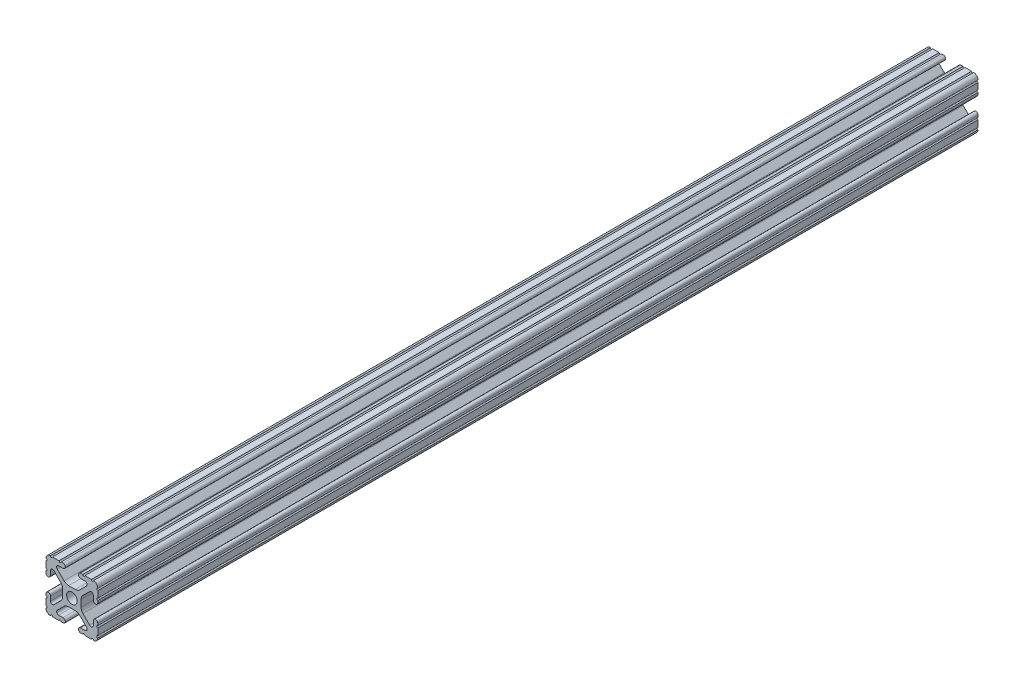
SolidWorks part; units mm, degrees
ref_plane "Front Plane" through (0, 0, 0) normal (0, 0, 1) x (1, 0, 0)
ref_plane "Top Plane" through (0, 0, 0) normal (0, 1, 0) x (1, 0, 0)
ref_plane "Right Plane" through (0, 0, 0) normal (1, 0, 0) x (0, 0, -1)
ref_plane "Plane1" through (0, 0, -1270) normal (0, 0, -1) x (-1, 0, 0)
sketch "Sketch1" plane through (0, 0, -1270) normal (0, 0, -1) x (-1, 0, 0)
  line L0 (12.7, -9.5504) -> (12.7, -6.3331)
  line L1 (12.7, -5.3171) -> (12.7, -4.3434)
  line L2 (10.4902, -4.3434) -> (10.4902, -6.4748)
  line L3 (8.7558, -7.1932) -> (5.4257, -3.8632)
  line L4 (4.4958, -1.6181) -> (4.4958, 1.6181)
  line L5 (5.4257, 3.8632) -> (8.7558, 7.1932)
  line L6 (10.4902, 6.4748) -> (10.4902, 4.3434)
  line L7 (12.7, 4.3434) -> (12.7, 5.3171)
  line L8 (12.7, 6.3331) -> (12.7, 9.5504)
  line L9 (9.5504, 12.7) -> (6.3331, 12.7)
  line L10 (5.3171, 12.7) -> (4.3434, 12.7)
  line L11 (4.3434, 10.4902) -> (6.4748, 10.4902)
  line L12 (7.1932, 8.7558) -> (3.8632, 5.4257)
  line L13 (1.6181, 4.4958) -> (-1.6181, 4.4958)
  line L14 (-3.8632, 5.4257) -> (-7.1932, 8.7558)
  line L15 (-6.4748, 10.4902) -> (-4.3434, 10.4902)
  line L16 (-4.3434, 12.7) -> (-5.3171, 12.7)
  line L17 (-6.3331, 12.7) -> (-9.5504, 12.7)
  line L18 (-12.7, 9.5504) -> (-12.7, 6.3331)
  line L19 (-12.7, 5.3171) -> (-12.7, 4.3434)
  line L20 (-10.4902, 4.3434) -> (-10.4902, 6.4748)
  line L21 (-8.7558, 7.1932) -> (-5.4257, 3.8632)
  line L22 (-4.4958, 1.6181) -> (-4.4958, -1.6181)
  line L23 (-5.4257, -3.8632) -> (-8.7558, -7.1932)
  line L24 (-10.4902, -6.4748) -> (-10.4902, -4.3434)
  line L25 (-12.7, -4.3434) -> (-12.7, -5.3171)
  line L26 (-12.7, -6.3331) -> (-12.7, -9.5504)
  line L27 (-9.5504, -12.7) -> (-6.3331, -12.7)
  line L28 (-5.3171, -12.7) -> (-4.3434, -12.7)
  line L29 (-4.3434, -10.4902) -> (-6.4748, -10.4902)
  line L30 (-7.1932, -8.7558) -> (-3.8632, -5.4257)
  line L31 (-1.6181, -4.4958) -> (1.6181, -4.4958)
  line L32 (3.8632, -5.4257) -> (7.1932, -8.7558)
  line L33 (6.4748, -10.4902) -> (4.3434, -10.4902)
  line L34 (4.3434, -12.7) -> (5.3171, -12.7)
  line L35 (6.3331, -12.7) -> (9.5504, -12.7)
  circle A0 centre (0, 0) radius 2.6035
  arc A1 (12.7, -6.3331) -> (12.7, -5.3171) centre (12.7, -5.8251) cw
  arc A2 (12.7, -4.3434) -> (10.4902, -4.3434) centre (11.5951, -4.3434) ccw
  arc A3 (10.4902, -6.4748) -> (8.7558, -7.1932) centre (9.4742, -6.4748) cw
  arc A4 (5.4257, -3.8632) -> (4.4958, -1.6181) centre (7.6708, -1.6181) cw
  arc A5 (4.4958, 1.6181) -> (5.4257, 3.8632) centre (7.6708, 1.6181) cw
  arc A6 (8.7558, 7.1932) -> (10.4902, 6.4748) centre (9.4742, 6.4748) cw
  arc A7 (10.4902, 4.3434) -> (12.7, 4.3434) centre (11.5951, 4.3434) ccw
  arc A8 (12.7, 5.3171) -> (12.7, 6.3331) centre (12.7, 5.8251) cw
  arc A9 (12.7, 9.5504) -> (12.6998, 10.5664) centre (12.7, 10.0584) cw
  arc A10 (12.6998, 10.5664) -> (10.5664, 12.6998) centre (10.5918, 10.5918) ccw
  arc A11 (10.5664, 12.6998) -> (9.5504, 12.7) centre (10.0584, 12.7) cw
  arc A12 (6.3331, 12.7) -> (5.3171, 12.7) centre (5.8251, 12.7) cw
  arc A13 (4.3434, 12.7) -> (4.3434, 10.4902) centre (4.3434, 11.5951) ccw
  arc A14 (6.4748, 10.4902) -> (7.1932, 8.7558) centre (6.4748, 9.4742) cw
  arc A15 (3.8632, 5.4257) -> (1.6181, 4.4958) centre (1.6181, 7.6708) cw
  arc A16 (-1.6181, 4.4958) -> (-3.8632, 5.4257) centre (-1.6181, 7.6708) cw
  arc A17 (-7.1932, 8.7558) -> (-6.4748, 10.4902) centre (-6.4748, 9.4742) cw
  arc A18 (-4.3434, 10.4902) -> (-4.3434, 12.7) centre (-4.3434, 11.5951) ccw
  arc A19 (-5.3171, 12.7) -> (-6.3331, 12.7) centre (-5.8251, 12.7) cw
  arc A20 (-9.5504, 12.7) -> (-10.5664, 12.6998) centre (-10.0584, 12.7) cw
  arc A21 (-10.5664, 12.6998) -> (-12.6998, 10.5664) centre (-10.5918, 10.5918) ccw
  arc A22 (-12.6998, 10.5664) -> (-12.7, 9.5504) centre (-12.7, 10.0584) cw
  arc A23 (-12.7, 6.3331) -> (-12.7, 5.3171) centre (-12.7, 5.8251) cw
  arc A24 (-12.7, 4.3434) -> (-10.4902, 4.3434) centre (-11.5951, 4.3434) ccw
  arc A25 (-10.4902, 6.4748) -> (-8.7558, 7.1932) centre (-9.4742, 6.4748) cw
  arc A26 (-5.4257, 3.8632) -> (-4.4958, 1.6181) centre (-7.6708, 1.6181) cw
  arc A27 (-4.4958, -1.6181) -> (-5.4257, -3.8632) centre (-7.6708, -1.6181) cw
  arc A28 (-8.7558, -7.1932) -> (-10.4902, -6.4748) centre (-9.4742, -6.4748) cw
  arc A29 (-10.4902, -4.3434) -> (-12.7, -4.3434) centre (-11.5951, -4.3434) ccw
  arc A30 (-12.7, -5.3171) -> (-12.7, -6.3331) centre (-12.7, -5.8251) cw
  arc A31 (-12.7, -9.5504) -> (-12.6998, -10.5664) centre (-12.7, -10.0584) cw
  arc A32 (-12.6998, -10.5664) -> (-10.5664, -12.6998) centre (-10.5918, -10.5918) ccw
  arc A33 (-10.5664, -12.6998) -> (-9.5504, -12.7) centre (-10.0584, -12.7) cw
  arc A34 (-6.3331, -12.7) -> (-5.3171, -12.7) centre (-5.8251, -12.7) cw
  arc A35 (-4.3434, -12.7) -> (-4.3434, -10.4902) centre (-4.3434, -11.5951) ccw
  arc A36 (-6.4748, -10.4902) -> (-7.1932, -8.7558) centre (-6.4748, -9.4742) cw
  arc A37 (-3.8632, -5.4257) -> (-1.6181, -4.4958) centre (-1.6181, -7.6708) cw
  arc A38 (1.6181, -4.4958) -> (3.8632, -5.4257) centre (1.6181, -7.6708) cw
  arc A39 (7.1932, -8.7558) -> (6.4748, -10.4902) centre (6.4748, -9.4742) cw
  arc A40 (4.3434, -10.4902) -> (4.3434, -12.7) centre (4.3434, -11.5951) ccw
  arc A41 (5.3171, -12.7) -> (6.3331, -12.7) centre (5.8251, -12.7) cw
  arc A42 (9.5504, -12.7) -> (10.5664, -12.6998) centre (10.0584, -12.7) cw
  arc A43 (10.5664, -12.6998) -> (12.6998, -10.5664) centre (10.5918, -10.5918) ccw
  arc A44 (12.6998, -10.5664) -> (12.7, -9.5504) centre (12.7, -10.0584) cw
extrude "Boss-Extrude1" add sketch "Sketch1" against normal blind 1270
ref_plane "Plane2" through (0, 0, -698.5) normal (0, 0, -1) x (-1, 0, 0)
sketch "Sketch6" plane through (0, 0, -698.5) normal (0, 0, -1) x (-1, 0, 0)
  line L0 (79.0024, -75.2236) -> (-43.6645, -75.2236)
  line L1 (79.0024, -75.2236) -> (79.0024, 34.1242)
  line L2 (79.0024, 34.1242) -> (-43.6645, 34.1242)
  line L3 (-43.6645, -75.2236) -> (-43.6645, 34.1242)
extrude "Cut-Extrude1" cut sketch "Sketch6" along normal through all
sketch "Sketch7" plane through (0, 0, 0) normal (0, 0, 1) x (1, 0, 0)
  line L1 (14.8387, -13.8646) -> (-14.8387, -13.8646)
  line L2 (14.8387, -13.8646) -> (14.8387, 13.8646)
  line L3 (14.8387, 13.8646) -> (-14.8387, 13.8646)
  line L4 (-14.8387, -13.8646) -> (-14.8387, 13.8646)
  line L5 (14.8387, -13.8646) -> (-14.8387, 13.8646) construction
  line L6 (14.8387, 13.8646) -> (-14.8387, -13.8646) construction
  point P0 (0, 0)
extrude "Cut-Extrude2" cut sketch "Sketch7" against normal blind 266.7
